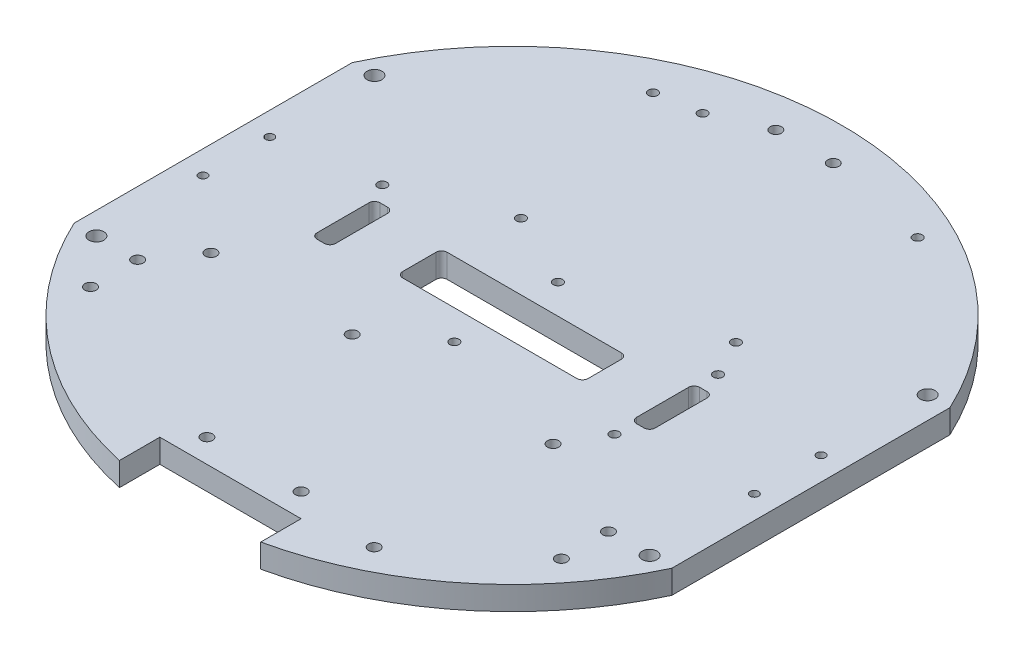
SolidWorks part; units mm, degrees
ref_plane "Front Plane" through (0, 0, 0) normal (0, 0, 1) x (1, 0, 0)
ref_plane "Top Plane" through (0, 0, 0) normal (0, 1, 0) x (1, 0, 0)
ref_plane "Right Plane" through (0, 0, 0) normal (1, 0, 0) x (0, 0, -1)
sketch "Sketch1" plane through (0, 0, 0) normal (0, 1, 0) x (1, 0, 0)
  line L0 (-80.6037, 37.5) -> (-80.6037, -37.5)
  line L1 (0, -88.9) -> (0, 88.9) construction
  line L2 (80.6037, 37.5) -> (80.6037, -37.5)
  arc A0 (-80.6037, -37.5) -> (80.6037, -37.5) centre (0, 0) ccw
  arc A1 (80.6037, 37.5) -> (-80.6037, 37.5) centre (0, 0) ccw
  dimension "D1" = 177.8
  dimension "D2" = 75
extrude "Main Body" add sketch "Sketch1" along normal blind 6.35
sketch "Sketch2" plane through (0, 6.35, 0) normal (0, 1, 0) x (1, 0, 0)
  line L0 (0, 88.9) -> (0, -88.9) construction
  line L1 (36.5, 72.9) -> (-21.5, 72.9) construction
  line L2 (36.5, 72.9) -> (36.5, 23.9) construction
  line L3 (36.5, 23.9) -> (-21.5, 23.9) construction
  line L4 (-21.5, 72.9) -> (-21.5, 23.9) construction
  line L5 (36.5, 72.9) -> (-21.5, 23.9) construction
  line L6 (36.5, 23.9) -> (-21.5, 72.9) construction
  circle A0 centre (36.5, 72.9) radius 1.25
  circle A1 centre (36.5, 23.9) radius 1.25
  circle A2 centre (-21.5, 23.9) radius 1.25
  circle A3 centre (-21.5, 72.9) radius 1.25
  arc A4 (-80.6037, -37.5) -> (80.6037, -37.5) centre (0, 0) ccw construction
  arc A5 (80.6037, 37.5) -> (-80.6037, 37.5) centre (0, 0) ccw construction
  point P0 (7.5, 48.4)
  point P11 (0, 88.9)
  dimension "D3" = 2.5
  dimension "D1" = 58
  dimension "D2" = 49
  dimension "D4" = 16
  dimension "D5" = 15
extrude "Raspberry Pi" cut sketch "Sketch2" against normal up to next
sketch "Sketch3" plane through (0, 6.35, 0) normal (0, 1, 0) x (1, 0, 0)
  line L0 (-80.6037, 0) -> (80.6037, 0) construction
  line L1 (-80.6037, 37.5) -> (-80.6037, -37.5) construction
  line L2 (80.6037, -37.5) -> (80.6037, 37.5) construction
  line L3 (-74.3537, -9) -> (-74.3537, 9) construction
  line L4 (0, -88.9) -> (0, 88.9) construction
  line L5 (74.3537, -9) -> (74.3537, 9) construction
  circle A0 centre (-74.3537, 9) radius 1.143
  circle A1 centre (-74.3537, -9) radius 1.143
  arc A2 (-80.6037, -37.5) -> (80.6037, -37.5) centre (0, 0) ccw construction
  arc A3 (80.6037, 37.5) -> (-80.6037, 37.5) centre (0, 0) ccw construction
  circle A4 centre (74.3537, 9) radius 1.143
  circle A5 centre (74.3537, -9) radius 1.143
  point P10 (-74.3537, 0)
  point P19 (74.3537, 0)
  dimension "D1" = 6.25
  dimension "D2" = 2.286
  dimension "D3" = 18
extrude "Motor Mounts" cut sketch "Sketch3" against normal up to next
sketch "Sketch4" plane through (0, 6.35, 0) normal (0, 1, 0) x (1, 0, 0)
  line L0 (0, -88.9) -> (0, 88.9) construction
  line L1 (-7.747, 78.9) -> (7.747, 78.9) construction
  arc A0 (-80.6037, -37.5) -> (80.6037, -37.5) centre (0, 0) ccw construction
  arc A1 (80.6037, 37.5) -> (-80.6037, 37.5) centre (0, 0) ccw construction
  circle A2 centre (-7.747, 78.9) radius 1.524
  circle A3 centre (7.747, 78.9) radius 1.524
  point P10 (0, 78.9)
  dimension "D1" = 3.048
  dimension "D2" = 15.494
  dimension "D3" = 10
extrude "Caster" cut sketch "Sketch4" against normal up to next
sketch "Sketch5" plane through (0, 6.35, 0) normal (0, 1, 0) x (1, 0, 0)
  line L0 (0, -88.9) -> (0, 88.9) construction
  line L1 (29.21, -82.5485) -> (29.21, 0.1133) construction
  line L2 (29.21, -24.4861) -> (50029.21, -24.4861) construction
  line L3 (29.21, -28.2961) -> (56.134, -28.2961) construction
  line L4 (29.21, -28.2961) -> (29.21, -68.9361) construction
  line L5 (29.21, -68.9361) -> (56.134, -68.9361) construction
  line L6 (56.134, -28.2961) -> (56.134, -68.9361) construction
  line L7 (29.21, -72.7461) -> (50029.21, -72.7461) construction
  line L8 (29.21, -28.2961) -> (29.21, -24.4861) construction
  line L9 (29.21, -68.9361) -> (29.21, -72.7461) construction
  line L10 (35.56, -24.4861) -> (35.56, -72.7461) construction
  arc A0 (-80.6037, -37.5) -> (80.6037, -37.5) centre (0, 0) ccw construction
  arc A1 (80.6037, 37.5) -> (-80.6037, 37.5) centre (0, 0) ccw construction
  circle A2 centre (35.56, -24.4861) radius 1.524
  circle A3 centre (35.56, -72.7461) radius 1.524
  dimension "D4" = 3.048
  dimension "D1" = 29.21
  dimension "D2" = 40.64
  dimension "D3" = 26.924
  dimension "D5" = 6.35
  dimension "D6" = 48.26
extrude "Grabber Mount" cut sketch "Sketch5" against normal through all
sketch "Sketch6" plane through (0, 6.35, 0) normal (0, 1, 0) x (1, 0, 0)
  line L0 (0, -88.1692) -> (0, -5.66) construction
  line L2 (-26.543, -75.692) -> (26.543, -75.692) construction
  line L3 (-26.543, -75.692) -> (-26.543, -63.5) construction
  line L4 (-26.543, -63.5) -> (26.543, -63.5) construction
  line L5 (26.543, -75.692) -> (26.543, -63.5) construction
  line L6 (-26.543, -75.692) -> (26.543, -63.5) construction
  line L7 (-26.543, -63.5) -> (26.543, -75.692) construction
  circle A0 centre (-12.7, -69.596) radius 1.524
  circle A1 centre (12.7, -69.596) radius 1.524
  point P1 (0, -69.596)
  dimension "D4" = 3.048
  dimension "D1" = 63.5
  dimension "D2" = 12.192
  dimension "D3" = 53.086
  dimension "D5" = 25.4
  dimension "D6" = 12.7
extrude "Front IR" cut sketch "Sketch6" against normal through all
sketch "Sketch8" plane through (0, 6.35, 0) normal (0, 1, 0) x (1, 0, 0)
  line L0 (0, 0) -> (0, 88.9) construction
  line L1 (-80.6037, 37.5) -> (-80.6037, -37.5) construction
  line L2 (-80.6037, -29.88) -> (80.6037, -29.88) construction
  line L3 (80.6037, -37.5) -> (80.6037, 37.5) construction
  line L4 (-80.6037, 23.206) -> (80.6037, 23.206) construction
  line L5 (0, 23.206) -> (0, -29.88) construction
  line L6 (0, -29.88) -> (0, -3.337) construction
  line L7 (-63.5, -37.5) -> (63.5, -37.5) construction
  circle A1 centre (-63.5, -37.5) radius 1.524
  circle A2 centre (-63.5, -50.2) radius 1.524
  circle A3 centre (63.5, -50.2) radius 1.524
  circle A4 centre (63.5, -37.5) radius 1.524
  dimension "D3" = 3.048
  dimension "D1" = 53.086
  dimension "D2" = 7.62
  dimension "D4" = 12.7
  dimension "D5" = 63.5
  dimension "D6" = 7.62
extrude "Side IR" cut sketch "Sketch8" against normal through all
sketch "Sketch9" plane through (0, 6.35, 0) normal (0, 1, 0) x (1, 0, 0)
  line L0 (35.56, -26.0101) -> (-80.6037, -26.0101) construction
  line L1 (-80.6037, 37.5) -> (-80.6037, -37.5) construction
  circle A0 centre (35.56, -24.4861) radius 1.524 construction
  circle A1 centre (-55.2037, -26.0101) radius 1.524
  circle A2 centre (-17.1037, -26.0101) radius 1.524
  dimension "D1" = 3.048
  dimension "D2" = 38.1
  dimension "D3" = 25.4
extrude "Pixy Mount" cut sketch "Sketch9" against normal through all
sketch "Sketch10" plane through (0, 6.35, 0) normal (0, 1, 0) x (1, 0, 0)
  line L0 (0, -88.9) -> (0, 0) construction
  line L1 (19.05, -101.854) -> (19.05, -75.946)
  line L2 (19.05, -101.854) -> (-19.05, -101.854)
  line L3 (19.05, -75.946) -> (-19.05, -75.946)
  line L4 (-19.05, -101.854) -> (-19.05, -75.946)
  line L5 (19.05, -101.854) -> (-19.05, -75.946) construction
  line L6 (19.05, -75.946) -> (-19.05, -101.854) construction
  arc A0 (-80.6037, -37.5) -> (80.6037, -37.5) centre (0, 0) ccw construction
  circle A1 centre (-12.7, -69.596) radius 1.524 construction
  dimension "D2" = 6.35
  dimension "D1" = 38.1
extrude "Grabber slot" cut sketch "Sketch10" against normal through all
sketch "Sketch11" plane through (0, 6.35, 0) normal (0, 1, 0) x (1, 0, 0)
  line L0 (0, 88.9) -> (0, -75.946) construction
  line L1 (19.05, -75.946) -> (-19.05, -75.946) construction
  line L2 (80.6037, 0) -> (-80.6037, 0) construction
  line L3 (80.6037, -37.5) -> (80.6037, 37.5) construction
  line L4 (-80.6037, 37.5) -> (-80.6037, -37.5) construction
  line L5 (-45.6037, 8.5) -> (-40.6037, 8.5)
  line L6 (25, -6) -> (-25, -6)
  line L7 (25, -6) -> (25, 6)
  line L8 (25, 6) -> (-25, 6)
  line L9 (-25, -6) -> (-25, 6)
  line L10 (25, -6) -> (-25, 6) construction
  line L11 (25, 6) -> (-25, -6) construction
  line L12 (45.6037, -8.5) -> (40.6037, -8.5)
  line L13 (45.6037, -8.5) -> (45.6037, 8.5)
  line L14 (45.6037, 8.5) -> (40.6037, 8.5)
  line L15 (40.6037, -8.5) -> (40.6037, 8.5)
  line L16 (45.6037, -8.5) -> (40.6037, 8.5) construction
  line L17 (45.6037, 8.5) -> (40.6037, -8.5) construction
  line L18 (-40.6037, -8.5) -> (-40.6037, 8.5)
  line L19 (-45.6037, -8.5) -> (-40.6037, -8.5)
  line L20 (-45.6037, -8.5) -> (-45.6037, 8.5)
  arc A0 (80.6037, 37.5) -> (-80.6037, 37.5) centre (0, 0) ccw construction
  point P13 (0, 0)
  point P19 (43.1037, 0)
  dimension "D3" = 35
  dimension "D1" = 12
  dimension "D2" = 50
  dimension "D4" = 17
  dimension "D5" = 5
extrude "Wire slots" cut sketch "Sketch11" against normal through all
sketch "Sketch13" plane through (0, 6.35, 0) normal (0, 1, 0) x (1, 0, 0)
  line L0 (0, 88.9) -> (0, -75.946) construction
  line L1 (19.05, -75.946) -> (-19.05, -75.946) construction
  line L2 (80.6037, 0) -> (-80.6037, 0) construction
  line L3 (80.6037, -37.5) -> (80.6037, 37.5) construction
  line L4 (-80.6037, 37.5) -> (-80.6037, -37.5) construction
  line L5 (80.6037, -37.5) -> (-80.6037, -37.5) construction
  line L6 (80.6037, 37.5) -> (-80.6037, 37.5) construction
  line L8 (74.6037, 37.5) -> (-74.6037, 37.5) construction
  line L9 (74.6037, 37.5) -> (74.6037, -37.5) construction
  line L10 (74.6037, -37.5) -> (-74.6037, -37.5) construction
  line L11 (-74.6037, 37.5) -> (-74.6037, -37.5) construction
  line L12 (74.6037, 37.5) -> (-74.6037, -37.5) construction
  line L13 (74.6037, -37.5) -> (-74.6037, 37.5) construction
  arc A0 (80.6037, 37.5) -> (-80.6037, 37.5) centre (0, 0) ccw construction
  circle A1 centre (74.6037, -37.5) radius 2
  circle A2 centre (-74.6037, -37.5) radius 2
  circle A3 centre (74.6037, 37.5) radius 2
  circle A4 centre (-74.6037, 37.5) radius 2
  point P21 (0, 0)
  dimension "D2" = 4
  dimension "D1" = 6
extrude "2nd level standoffs" cut sketch "Sketch13" against normal through all
fillet "Fillet1" radius 1.5 12 edges at (40.6037, 3.175, -8.5) (40.6037, 3.175, 8.5) (45.6037, 3.175, 8.5) (45.6037, 3.175, -8.5) (-45.6037, 3.175, 8.5) (-40.6037, 3.175, 8.5) (-45.6037, 3.175, -8.5) (-40.6037, 3.175, -8.5) (-25, 3.175, 6) (-25, 3.175, -6) (25, 3.175, 6) (25, 3.175, -6)
sketch "Sketch14" plane through (0, 6.35, 0) normal (0, 1, 0) x (1, 0, 0)
  line L0 (80.6037, 0) -> (-80.6037, 0) construction
  line L1 (-1.59, -13.97) -> (41.59, -13.97) construction
  line L2 (-1.59, -13.97) -> (-1.59, 13.97) construction
  line L3 (-1.59, 13.97) -> (41.59, 13.97) construction
  line L4 (41.59, -13.97) -> (41.59, 13.97) construction
  line L5 (-1.59, -13.97) -> (41.59, 13.97) construction
  line L6 (-1.59, 13.97) -> (41.59, -13.97) construction
  line L7 (80.6037, -37.5) -> (80.6037, 37.5) construction
  line L8 (-80.6037, 37.5) -> (-80.6037, -37.5) construction
  circle A0 centre (-1.59, 13.97) radius 1.25
  circle A1 centre (41.59, 13.97) radius 1.25
  circle A2 centre (41.59, -13.97) radius 1.25
  circle A3 centre (-1.59, -13.97) radius 1.25
  point P0 (20, 0)
  dimension "D3" = 2.5
  dimension "D1" = 43.18
  dimension "D2" = 27.94
  dimension "D4" = 20
extrude "Encoder Perfboard" cut sketch "Sketch14" against normal blind 10
sketch "Sketch15" plane through (0, 6.35, 0) normal (0, 1, 0) x (1, 0, 0)
  line L1 (-30, 74) -> (-51, 74) construction
  line L2 (-30, 74) -> (-30, 10) construction
  line L3 (-30, 10) -> (-51, 10) construction
  line L4 (-51, 74) -> (-51, 10) construction
  line L5 (-30, 74) -> (-51, 10) construction
  line L6 (-30, 10) -> (-51, 74) construction
  circle A0 centre (-48, 13) radius 1.25
  circle A1 centre (-33, 71) radius 1.25
  point P0 (-40.5, 42)
  dimension "D6" = 3
  dimension "D7" = 2.5
  dimension "D9" = 3
  dimension "D10" = 2.5
  dimension "D1" = 21
  dimension "D2" = 64
  dimension "D3" = 10
  dimension "D4" = 30
  dimension "D5" = 3
  dimension "D8" = 3
extrude "decoder ic" cut sketch "Sketch15" against normal blind 10
